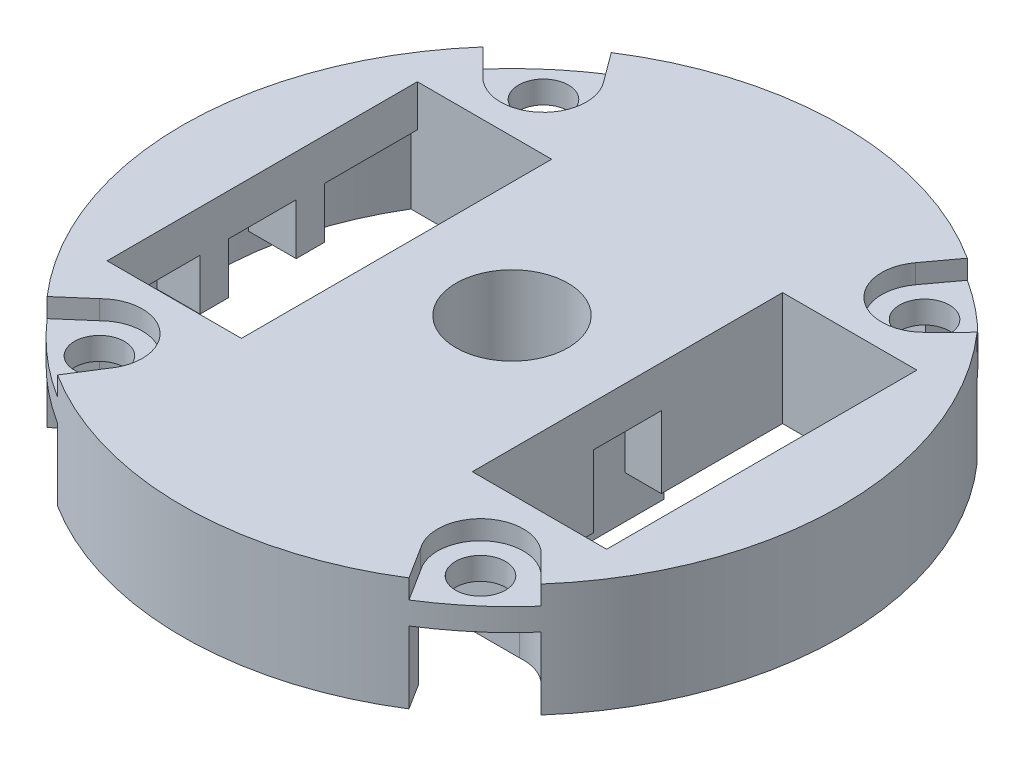
SolidWorks part; units mm, degrees
ref_plane "Front Plane" through (0, 0, 0) normal (0, 0, 1) x (1, 0, 0)
ref_plane "Top Plane" through (0, 0, 0) normal (0, 1, 0) x (1, 0, 0)
ref_plane "Right Plane" through (0, 0, 0) normal (1, 0, 0) x (0, 0, -1)
sketch "Sketch1" plane through (0, 0, 0) normal (0, 1, 0) x (1, 0, 0)
  line L0 (-15.825, 0) -> (15.825, 0) construction
  line L1 (0, -55) -> (0, 55) construction
  line L2 (5.545, 7.45) -> (11.995, 7.45)
  line L3 (5.545, 7.45) -> (5.545, -7.45)
  line L4 (5.545, -7.45) -> (11.995, -7.45)
  line L5 (11.995, 7.45) -> (11.995, -7.45)
  line L6 (-5.545, -7.45) -> (-11.995, -7.45)
  line L7 (-11.995, 7.45) -> (-11.995, -7.45)
  line L8 (-5.545, 7.45) -> (-11.995, 7.45)
  line L9 (-5.545, 7.45) -> (-5.545, -7.45)
  line L10 (-10.6107, 9.2095) -> (-11.8653, 10.4712)
  line L11 (-7.4926, 11.8854) -> (-8.5492, 13.317)
  line L12 (7.4926, 11.8854) -> (8.5492, 13.317)
  line L13 (10.6107, 9.2095) -> (11.8653, 10.4712)
  line L14 (10.6107, -9.2095) -> (11.8653, -10.4712)
  line L15 (7.4926, -11.8854) -> (8.4392, -13.387)
  line L16 (-7.4926, -11.8854) -> (-8.4392, -13.387)
  line L17 (-10.6107, -9.2095) -> (-11.9512, -10.373)
  circle A0 centre (0, 0) radius 15.825
  circle A1 centre (0, 0) radius 2.69
  circle A2 centre (0, 0) radius 14.05 construction
  circle A3 centre (-9.15, 10.6621) radius 1.2
  circle A4 centre (9.15, 10.6621) radius 1.2
  circle A5 centre (9.15, -10.6621) radius 1.2
  circle A6 centre (-9.15, -10.6621) radius 1.2
  arc A8 (-10.6107, 9.2095) -> (-7.4926, 11.8854) centre (-9.15, 10.6621) ccw
  arc A9 (7.4926, 11.8854) -> (10.6107, 9.2095) centre (9.15, 10.6621) ccw
  arc A11 (-7.4926, -11.8854) -> (-10.6107, -9.2095) centre (-9.15, -10.6621) ccw
  arc A12 (10.6107, -9.2095) -> (7.4926, -11.8854) centre (9.15, -10.6621) ccw
  point P7 (11.995, 0)
  point P14 (9.15, 10.6621)
  point P15 (9.15, -10.6621)
  point P16 (-9.15, -10.6621)
  point P18 (-9.15, 10.6621)
  dimension "D1" = 31.65
  dimension "D2" = 5.38
  dimension "D6" = 28.1
  dimension "D8" = 2.4
  dimension "D9" = 2.4
  dimension "D10" = 2.4
  dimension "D11" = 2.4
  dimension "D12" = 4.12
  dimension "D13" = 4.12
  dimension "D14" = 4.12
  dimension "D15" = 4.12
  dimension "D3" = 14.9
  dimension "D4" = 6.45
  dimension "D5" = 3.83
  dimension "D7" = 18.3
extrude "Boss-Extrude1" add sketch "Sketch1" along normal blind 2 contours A12 L14 A0 L13 A9 L12 L11 A8 L10 L17 A11 L16 L15 A1 L8 L9 L6 L7 L2 L5 L4 L3 region at (-7.5169, 0, -8.7591)
extrude "Boss-Extrude2" add sketch "Sketch1<4>" along normal blind 1.08 contours L16 A11 L17 A0 A6 | L10 A8 L11 A0 A3 | L12 A9 L13 A0 A4 | L14 A12 L15 A0 A5 region at (-11.1904, 0, -9.8877) region at (-11.2362, 0, 9.8428) region at (10.2623, 0, -11.9581) region at (8.0231, 0, 12.6002)
sketch "Sketch1<4>" plane through (0, 0, 0) normal (0, 1, 0) x (1, 0, 0) same geometry as "Sketch1"
sketch "Sketch2" plane through (0, 0, 0) normal (0, 1, 0) x (1, 0, 0)
  line L0 (-5.545, 7.45) -> (-11.995, 7.45) construction
  line L1 (-11.995, 7.45) -> (-11.995, -7.45) construction
  line L2 (-5.545, -7.45) -> (-11.995, -7.45) construction
  line L3 (-5.545, 7.45) -> (-5.545, -7.45) construction
  line L4 (5.545, 7.45) -> (11.995, 7.45) construction
  line L5 (11.995, 7.45) -> (11.995, -7.45) construction
  line L6 (5.545, -7.45) -> (11.995, -7.45) construction
  line L7 (5.545, 7.45) -> (5.545, -7.45) construction
  line L8 (-5.545, 7.45) -> (-11.995, 7.45)
  line L9 (-11.995, 7.45) -> (-11.995, -7.45)
  line L10 (-5.545, -7.45) -> (-11.995, -7.45)
  line L11 (-5.545, 7.45) -> (-5.545, -7.45)
  line L12 (5.545, 7.45) -> (11.995, 7.45)
  line L13 (11.995, 2.98) -> (11.995, 1.63)
  line L14 (5.545, -7.45) -> (11.995, -7.45)
  line L15 (5.545, 7.45) -> (5.545, -7.45)
  line L16 (0, -1.1) -> (0, 1.1) construction
  line L17 (4.385, -8.61) -> (9.3304, -8.61)
  line L18 (4.385, -8.61) -> (4.385, -3.5)
  line L19 (4.385, 8.61) -> (9.3304, 8.61)
  line L21 (-4.385, 8.61) -> (-9.3304, 8.61)
  line L23 (-4.385, -8.61) -> (-9.3304, -8.61)
  line L24 (-4.385, -8.61) -> (-4.385, -3.5)
  line L25 (10.6107, 9.2095) -> (11.8653, 10.4712) construction
  line L26 (7.4926, 11.8854) -> (8.5492, 13.317) construction
  line L27 (-7.4926, 11.8854) -> (-8.5492, 13.317) construction
  line L28 (-10.6107, 9.2095) -> (-11.8653, 10.4712) construction
  line L29 (-10.6107, -9.2095) -> (-11.9512, -10.373) construction
  line L30 (-7.4926, -11.8854) -> (-8.4392, -13.387) construction
  line L31 (10.6107, -9.2095) -> (11.8653, -10.4712) construction
  line L32 (7.4926, -11.8854) -> (8.4392, -13.387) construction
  line L33 (10.6107, 9.2095) -> (11.8653, 10.4712)
  line L34 (7.4926, 11.8854) -> (8.5492, 13.317)
  line L35 (-7.4926, 11.8854) -> (-8.5492, 13.317)
  line L36 (-10.6107, 9.2095) -> (-11.8653, 10.4712)
  line L37 (-10.6107, -9.2095) -> (-11.9512, -10.373)
  line L38 (-7.4926, -11.8854) -> (-8.4392, -13.387)
  line L39 (10.6107, -9.2095) -> (11.8653, -10.4712)
  line L40 (7.4926, -11.8854) -> (8.4392, -13.387)
  line L41 (-15.825, 0) -> (15.825, 0) construction
  line L42 (11.995, -1.63) -> (14.2924, -1.63)
  line L43 (11.995, 1.63) -> (14.2924, 1.63)
  line L44 (13.0177, -1.63) -> (13.0177, 1.63) construction
  line L45 (11.995, -2.98) -> (14.0729, -2.98)
  line L46 (11.995, 2.98) -> (14.0729, 2.98)
  line L47 (11.995, -1.63) -> (11.995, -2.98)
  line L48 (11.995, -7.45) -> (12.3055, -7.45)
  line L49 (11.995, 7.45) -> (12.3055, 7.45)
  line L50 (-13.0177, -1.63) -> (-13.0177, 1.63) construction
  line L51 (-11.995, 2.98) -> (-14.0729, 2.98)
  line L52 (-11.995, 1.63) -> (-14.2924, 1.63)
  line L53 (-11.995, -1.63) -> (-14.2924, -1.63)
  line L54 (-11.995, -2.98) -> (-14.0729, -2.98)
  line L55 (-11.995, -7.45) -> (-12.3055, -7.45)
  line L56 (-11.995, 7.45) -> (-12.3055, 7.45)
  line L57 (5.545, -1.63) -> (4.385, -1.63)
  line L58 (5.545, 1.63) -> (4.385, 1.63)
  line L59 (-5.545, 1.63) -> (-4.385, 1.63)
  line L60 (-5.545, -1.63) -> (-4.385, -1.63)
  line L61 (0, -3.5) -> (-4.385, -3.5)
  line L62 (0, -3.5) -> (4.385, -3.5)
  line L63 (0, 3.5) -> (-4.385, 3.5)
  line L64 (0, 3.5) -> (4.385, 3.5)
  line L65 (-2.9784, -3.5) -> (-2.9784, 3.5) construction
  line L66 (4.385, 3.5) -> (4.385, 8.61)
  line L67 (-4.385, 3.5) -> (-4.385, 8.61)
  line L68 (-3.795, -1.63) -> (-3.795, 1.63)
  line L69 (3.795, -1.63) -> (3.795, 1.63)
  line L70 (-4.385, -1.63) -> (-3.795, -1.63)
  line L71 (-4.385, 1.63) -> (-3.795, 1.63)
  line L72 (3.795, -1.63) -> (4.385, -1.63)
  line L73 (3.795, 1.63) -> (4.385, 1.63)
  line L74 (-3.795, -3.5) -> (-3.795, -1.63)
  line L75 (3.795, -3.5) -> (3.795, -1.63)
  line L76 (3.795, 1.63) -> (3.795, 3.5)
  line L77 (-3.795, 1.63) -> (-3.795, 3.5)
  circle A0 centre (9.15, 10.6621) radius 1.2 construction
  circle A1 centre (-9.15, 10.6621) radius 1.2 construction
  circle A2 centre (9.15, -10.6621) radius 1.2 construction
  circle A3 centre (0, 0) radius 2.69 construction
  circle A4 centre (0, 0) radius 15.825 construction
  circle A5 centre (9.15, 10.6621) radius 1.2
  circle A6 centre (-9.15, 10.6621) radius 1.2
  circle A7 centre (9.15, -10.6621) radius 1.2
  circle A8 centre (0, 0) radius 2.69
  circle A9 centre (0, 0) radius 15.825
  arc A10 (7.4926, 11.8854) -> (10.6107, 9.2095) centre (9.15, 10.6621) ccw construction
  arc A11 (-10.6107, 9.2095) -> (-7.4926, 11.8854) centre (-9.15, 10.6621) ccw construction
  arc A12 (-7.4926, -11.8854) -> (-10.6107, -9.2095) centre (-9.15, -10.6621) ccw construction
  arc A13 (10.6107, -9.2095) -> (7.4926, -11.8854) centre (9.15, -10.6621) ccw construction
  arc A14 (7.4926, 11.8854) -> (10.6107, 9.2095) centre (9.15, 10.6621) ccw
  arc A15 (-10.6107, 9.2095) -> (-7.4926, 11.8854) centre (-9.15, 10.6621) ccw
  arc A16 (-7.4926, -11.8854) -> (-10.6107, -9.2095) centre (-9.15, -10.6621) ccw
  arc A17 (10.6107, -9.2095) -> (7.4926, -11.8854) centre (9.15, -10.6621) ccw
  arc A18 (-12.3055, 7.45) -> (-12.3055, -7.45) centre (0, 0) ccw
  arc A19 (-7.6712, -12.1688) -> (7.6712, -12.1688) centre (0, 0) ccw
  arc A21 (7.6921, 12.1557) -> (-7.6921, 12.1557) centre (0, 0) ccw
  arc A22 (12.3055, 7.45) -> (12.3055, -7.45) centre (0, 0) cw
  circle A24 centre (0, 0) radius 3.5
  point P69 (13.0177, 0)
  point P74 (-13.0177, 0)
  point P105 (-2.9784, 0)
  dimension "D5" = 1.44
  dimension "D2" = 1.44
  dimension "D9" = 7
  dimension "D1" = 1.16
  dimension "D3" = 1.16
  dimension "D4" = 1.16
  dimension "D6" = 3.26
  dimension "D7" = 1.35
  dimension "D8" = 1.35
  dimension "D10" = 1.75
  dimension "D11" = 1.75
extrude "Boss-Extrude3" add sketch "Sketch2" against normal blind 3.45 separate body contours A17 L39 A9 L33 A14 L19 L66 L64 L63 L67 L21 A15 L36 L37 A16 L23 L24 L61 L62 L18 L17 A18 L56 L8 L11 L59 L71 L68 L70 L60 L10 L55 A8 L49 A22 | A24 L62 L18 L17 A17 L39 A9 L33 A14 L19 L66 L64 L49 A22 L48 L14 L15 L57 L72 L69 L73 L58 L12 | A24 L62 L69 L64 | A24 L63 L68 L61 | A24 A8 region at (-8.77, 0, -7.6907) region at (-3.7154, 0, -2.565) region at (1.8975, 0, -3.4204) region at (2.4049, 0, -2.4049) region at (4.09, 0, -3.2585)
extrude "Boss-Extrude4" add sketch "Sketch2<3>" against normal blind 3.45 contours A21 L34 A9 L35 | A19 L38 A9 L40 region at (-7.9799, 0, -12.8402) region at (0, 0, 14.5577)
sketch "Sketch2<3>" plane through (0, 0, 0) normal (0, 1, 0) x (1, 0, 0) same geometry as "Sketch2"
extrude "Boss-Extrude5" add sketch "Sketch2<4>" against normal blind 2.45 contours L53 A18 L54 L9 | L51 A18 L52 L9 | A22 L42 L47 L45 | A22 L46 L13 L43 region at (-13.0952, 0, -2.2938) region at (-13.0952, 0, 2.2938) region at (13.0952, 0, -2.2938) region at (13.0952, 0, 2.2938)
sketch "Sketch2<4>" plane through (0, 0, 0) normal (0, 1, 0) x (1, 0, 0) same geometry as "Sketch2"
extrude "Boss-Extrude6" add sketch "Sketch2<5>" against normal blind 3.45 contours A24 A8 region at (2.4049, 0, -2.4049)
sketch "Sketch2<5>" plane through (0, 0, 0) normal (0, 1, 0) x (1, 0, 0) same geometry as "Sketch2"
extrude "Boss-Extrude7" add sketch "Sketch2<6>" against normal blind 5.5 contours A24 A8 | A24 L62 L75 L69 L76 L64 | A24 L63 L77 L68 L74 L61 region at (-3.7154, 0, -2.565) region at (1.8975, 0, -3.4204) region at (2.4049, 0, -2.4049)
sketch "Sketch2<6>" plane through (0, 0, 0) normal (0, 1, 0) x (1, 0, 0) same geometry as "Sketch2"
